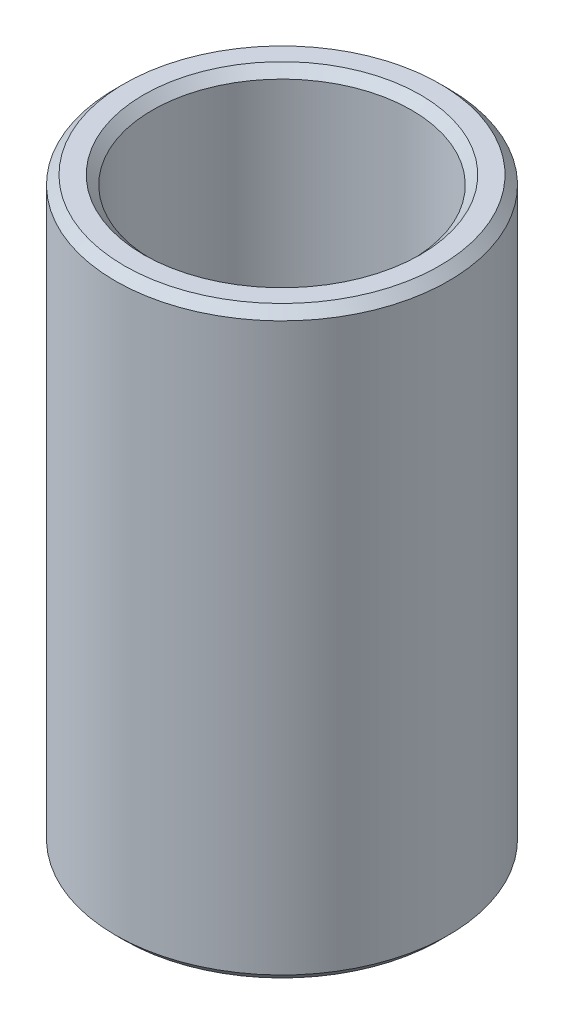
SolidWorks part; units mm, degrees
ref_plane "Front Plane" through (0, 0, 0) normal (0, 0, 1) x (1, 0, 0)
ref_plane "Top Plane" through (0, 0, 0) normal (0, 1, 0) x (1, 0, 0)
ref_plane "Right Plane" through (0, 0, 0) normal (1, 0, 0) x (0, 0, -1)
sketch "Sketch1" plane through (0, 0, 0) normal (0, 1, 0) x (1, 0, 0)
  circle A0 centre (0, 0) radius 50
  dimension "SLEEVE_OD" = 100
extrude "Boss-Extrude1" add sketch "Sketch1" along normal blind 175.3588
sketch "Sketch2" plane through (0, 0, 0) normal (0, 1, 0) x (1, 0, 0)
  circle A0 centre (0, 0) radius 38.9108
  dimension "BORE_D" = 77.8216
extrude "Cut-Extrude1" cut sketch "Sketch2" along normal through all
chamfer "Chamfer1" distance 2.6514 angle 45 4 edges at (0, 175.3588, 38.9108) (0, 0, 38.9108) (0, 0, 50) (0, 175.3588, 50)
